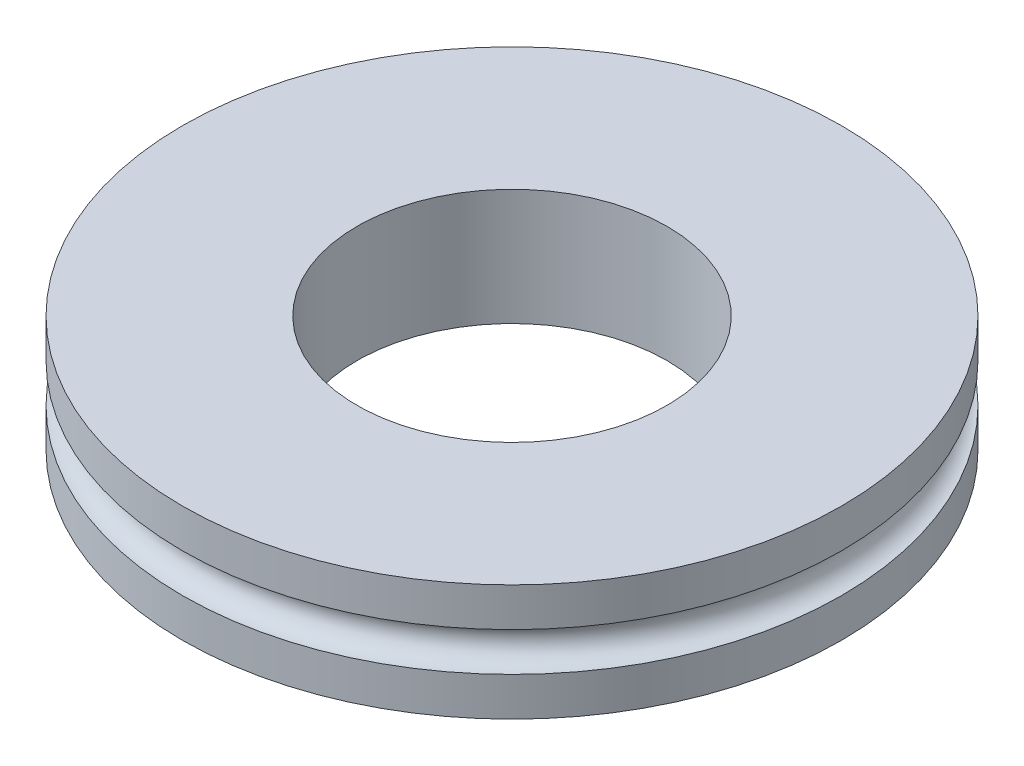
SolidWorks part; units mm, degrees
ref_plane "Front Plane" through (0, 0, 0) normal (0, 0, 1) x (1, 0, 0)
ref_plane "Top Plane" through (0, 0, 0) normal (0, 1, 0) x (1, 0, 0)
ref_plane "Right Plane" through (0, 0, 0) normal (1, 0, 0) x (0, 0, -1)
sketch "Sketch1" plane through (0, 0, 0) normal (0, 0, 1) x (1, 0, 0)
  line L0 (0, -1.5) -> (0, 1.5) construction
  line L1 (0, 1.5) -> (8.5, 1.5) construction
  line L2 (8.5, 1.5) -> (8.5, -1.5) construction
  line L3 (8.5, -1.5) -> (0, -1.5) construction
  line L4 (4, 1.5) -> (4, -1.5)
  line L5 (4, 0.5) -> (8.5, 0.5) construction
  line L6 (4, -0.5) -> (8.5, -0.5) construction
  line L7 (8.5, -0.5) -> (8.5, -1.5)
  line L8 (8.5, -1.5) -> (4, -1.5)
  line L9 (4, 1.5) -> (8.5, 1.5)
  line L10 (8.5, 1.5) -> (8.5, 0.5)
  line L11 (4, 0) -> (8, 0) construction
  arc A0 (8.5, 0.5) -> (8.5, -0.5) centre (8.5, 0) ccw
  point P4 (0, 0)
  point P16 (0, 0)
  dimension "D2" = 8
  dimension "D3" = 1
  dimension "D1" = 4
  dimension "D4" = 1
revolve "Revolve1" add sketch "Sketch1" angle 360 about L0
